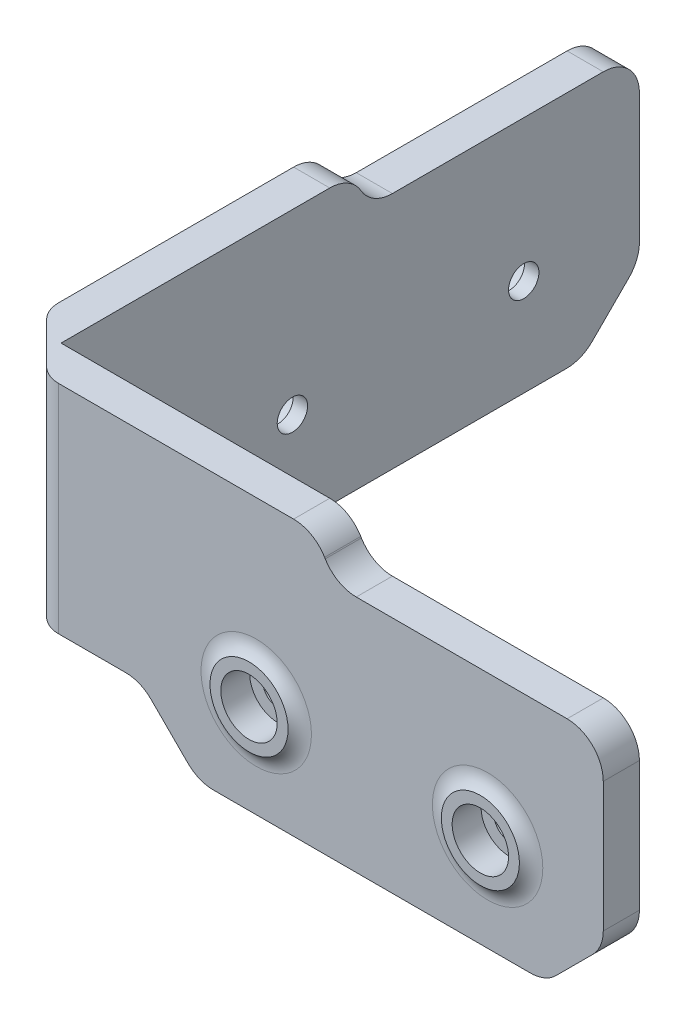
SolidWorks part; units mm, degrees
ref_plane "Front Plane" through (0, 0, 0) normal (0, 0, 1) x (1, 0, 0)
ref_plane "Top Plane" through (0, 0, 0) normal (0, 1, 0) x (1, 0, 0)
ref_plane "Right Plane" through (0, 0, 0) normal (1, 0, 0) x (0, 0, -1)
sketch "Sketch1" plane through (0, 0, 0) normal (0, 0, 1) x (1, 0, 0)
  line L0 (-255, 28) -> (-255, -2)
  line L1 (-226, -10) -> (-178, -10)
  line L2 (-170, -2) -> (-170, 23)
  line L3 (-170, 23) -> (-207, 23)
  line L4 (-207, 23) -> (-210, 28)
  line L5 (-210, 28) -> (-255, 28)
  line L6 (-247, 28) -> (-210.5662, 28) construction
  line L7 (-209.7087, 27.5145) -> (-207, 23) construction
  line L8 (-206.4338, 23) -> (-171, 23) construction
  line L9 (-170, 22) -> (-170, 13) construction
  line L10 (-250, 10) -> (-250, -290) construction
  line L11 (-230, -10) -> (230, -10) construction
  line L12 (-255, -2) -> (-234, -2)
  line L13 (-234, -2) -> (-226, -10)
  line L14 (-178, -10) -> (-170, -2)
  point P3 (-170, -10)
  dimension "D1" = 5
  dimension "D2" = 64
extrude "Boss-Extrude1" add sketch "Sketch1" along normal blind 5
ref_plane "Plane1" through (-125, 0, -125) normal (-0.7071, 0, -0.7071) x (0, -1, 0)
mirror "Mirror1" about plane through (-125, 0, -125) normal (-0.7071, 0, -0.7071) of "Boss-Extrude1"
fillet "Fillet1" radius 5 14 edges at (-207, 23, 2.5) (-170, 23, 2.5) (-170, -2, 2.5) (-178, -10, 2.5) (-226, -10, 2.5) (-234, -2, 2.5) (-210, 28, 2.5) (-252.5, 28, -40) (-252.5, 23, -43) (-252.5, 23, -80) (-252.5, -10, -72) (-252.5, -2, -80) (-252.5, -10, -24) (-252.5, -2, -16)
chamfer "Chamfer1" distance 8 angle 45 1 edges at (-255, 13, 5)
fillet "Fillet2" radius 4 2 edges at (-247, 13, 5) (-255, 13, -3)
sketch "Sketch2" plane through (0, 0, 5) normal (0, 0, 1) x (1, 0, 0)
  line L0 (-170, 3.4251) -> (-218, 3.4251) construction
  line L1 (-170, 0.0711) -> (-170, 18) construction
  line L2 (-230, 3.4251) -> (230, 3.4251) construction
  circle A0 centre (-218, 3.4251) radius 2.1
  circle A1 centre (-186, 3.4251) radius 2.1
  dimension "D1" = 4.2
  dimension "D2" = 16
  dimension "D3" = 32
extrude "Cut-Extrude1" cut sketch "Sketch2" against normal through all
sketch "Sketch3" plane through (0, 0, 5) normal (0, 0, 1) x (1, 0, 0)
  circle A0 centre (-218, 3.4251) radius 3.9
  circle A1 centre (-186, 3.4251) radius 3.9
  dimension "D1" = 7.8
extrude "Cut-Extrude2" cut sketch "Sketch3" against normal blind 3
sketch "Sketch4" plane through (0, 0, 5) normal (0, 0, 1) x (1, 0, 0)
  circle A0 centre (-186, 3.4251) radius 3.9 construction
  circle A1 centre (-218, 3.4251) radius 3.9 construction
  circle A2 centre (-186, 3.4251) radius 3.9
  circle A3 centre (-218, 3.4251) radius 3.9
  circle A4 centre (-218, 3.4251) radius 5.4
  circle A5 centre (-186, 3.4251) radius 5.4
  dimension "D1" = 1.5
extrude "Boss-Extrude2" add sketch "Sketch4" along normal blind 1
mirror "Mirror2" about plane through (-125, 0, -125) normal (-0.7071, 0, -0.7071) of "Boss-Extrude2", "Cut-Extrude2", "Cut-Extrude1"
fillet "Fillet3" radius 3 4 edges at (-255, 3.4251, -37.4) (-255, 3.4251, -69.4) (-212.6, 3.4251, 5) (-180.6, 3.4251, 5)
